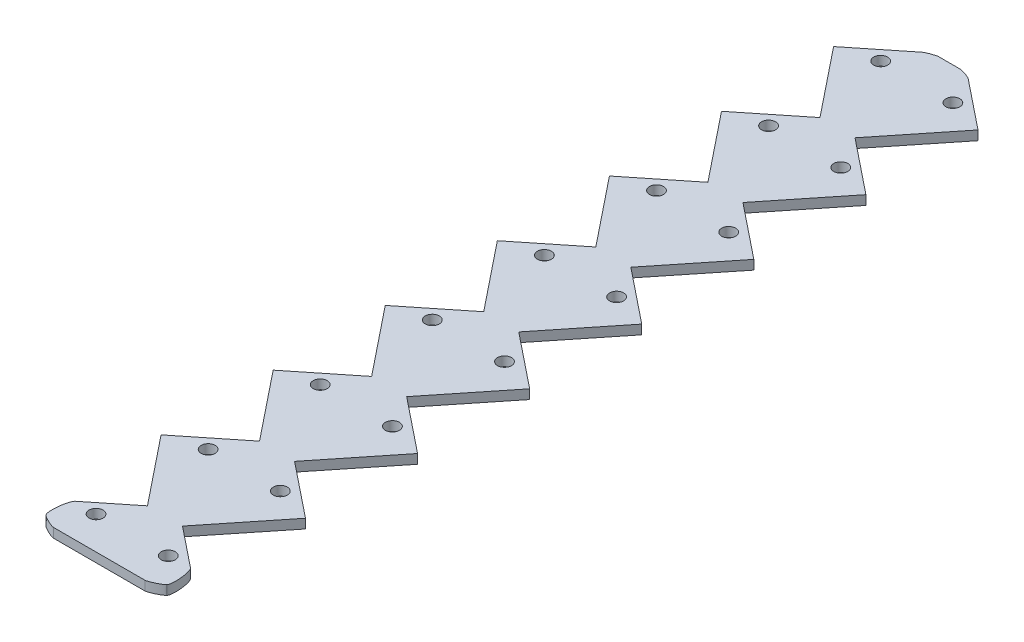
SolidWorks part; units mm, degrees
ref_plane "Front Plane" through (0, 0, 0) normal (0, 0, 1) x (1, 0, 0)
ref_plane "Top Plane" through (0, 0, 0) normal (0, 1, 0) x (1, 0, 0)
ref_plane "Right Plane" through (0, 0, 0) normal (1, 0, 0) x (0, 0, -1)
sketch "Sketch1" plane through (0, 0, 0) normal (0, 1, 0) x (1, 0, 0)
  line L0 (-13.635, -43.1454) -> (0.2556, -60.4948) construction
  line L5 (-13.635, -43.1454) -> (-22.9293, -50.5868) construction
  line L6 (-22.9293, -50.5868) -> (-9.0387, -67.9362) construction
  line L7 (-22.1678, 36.7724) -> (28.6322, 36.7724) construction
  line L8 (-22.1678, 36.7724) -> (-22.1678, -191.8276) construction
  line L9 (-22.1678, -191.8276) -> (28.6322, -191.8276) construction
  line L10 (28.6322, 36.7724) -> (28.6322, -191.8276) construction
  line L11 (0.2556, -60.4948) -> (-9.0387, -67.9362) construction
  line L12 (-13.635, -24.0954) -> (0.2556, -41.4448) construction
  line L13 (-13.635, -24.0954) -> (-22.9293, -31.5368) construction
  line L14 (-22.9293, -31.5368) -> (-9.0387, -48.8862) construction
  line L15 (-8.1122, -59.5683) -> (-27.1622, -59.5683) construction
  line L16 (-8.1122, -59.5683) -> (-8.1122, -40.5183) construction
  line L17 (0.2556, -41.4448) -> (-9.0387, -48.8862) construction
  line L18 (-8.1122, -40.5183) -> (-27.1622, -40.5183) construction
  line L19 (-8.1122, -40.5183) -> (-8.1122, -21.4683) construction
  line L20 (-13.635, -100.2954) -> (0.2556, -117.6448) construction
  line L21 (-13.635, -100.2954) -> (-22.9293, -107.7368) construction
  line L22 (-22.9293, -107.7368) -> (-9.0387, -125.0862) construction
  line L23 (0.2556, -117.6448) -> (-9.0387, -125.0862) construction
  line L24 (-13.635, -81.2454) -> (0.2556, -98.5948) construction
  line L25 (-13.635, -81.2454) -> (-22.9293, -88.6868) construction
  line L26 (-22.9293, -88.6868) -> (-9.0387, -106.0362) construction
  line L27 (-8.1122, -116.7183) -> (-27.1622, -116.7183) construction
  line L28 (-8.1122, -116.7183) -> (-8.1122, -97.6683) construction
  line L29 (0.2556, -98.5948) -> (-9.0387, -106.0362) construction
  line L30 (-8.1122, -97.6683) -> (-27.1622, -97.6683) construction
  line L31 (-8.1122, -97.6683) -> (-8.1122, -78.6183) construction
  line L32 (-13.635, -5.0454) -> (0.2556, -22.3948) construction
  line L33 (-13.635, -5.0454) -> (-22.9293, -12.4868) construction
  line L34 (-13.635, 14.0046) -> (0.2556, -3.3448) construction
  line L35 (-13.635, 14.0046) -> (-22.9293, 6.5632) construction
  line L36 (-22.9293, 6.5632) -> (-9.0387, -10.7862) construction
  line L37 (0.2556, -3.3448) -> (-9.0387, -10.7862) construction
  line L38 (-22.9293, -12.4868) -> (-9.0387, -29.8362) construction
  line L39 (0.2556, -22.3948) -> (-9.0387, -29.8362) construction
  line L40 (-13.635, 33.0546) -> (0.2556, 15.7052) construction
  line L41 (-13.635, 33.0546) -> (-22.9293, 25.6132) construction
  line L42 (-22.9293, 25.6132) -> (-9.0387, 8.2638) construction
  line L43 (0.2556, 15.7052) -> (-9.0387, 8.2638) construction
  line L44 (-8.1122, -21.4683) -> (-27.1622, -21.4683) construction
  line L45 (-8.1122, -21.4683) -> (-8.1122, -2.4183) construction
  line L46 (-13.635, -62.1954) -> (0.2556, -79.5448) construction
  line L47 (-13.635, -62.1954) -> (-22.9293, -69.6368) construction
  line L48 (-22.9293, -69.6368) -> (-9.0387, -86.9862) construction
  line L49 (0.2556, -79.5448) -> (-9.0387, -86.9862) construction
  line L50 (-8.1122, -78.6183) -> (-27.1622, -78.6183) construction
  line L51 (-8.1122, -78.6183) -> (-8.1122, -59.5683) construction
  line L52 (-8.1122, -2.4183) -> (-27.1622, -2.4183) construction
  line L53 (-8.1122, -2.4183) -> (-8.1122, 16.6317) construction
  line L54 (-8.1122, 16.6317) -> (-27.1622, 16.6317) construction
  line L55 (-8.1122, 16.6317) -> (-8.1122, 35.6817) construction
  line L56 (-22.9293, 25.6132) -> (-25.9059, 29.3309) construction
  line L57 (-25.9059, 29.3309) -> (-16.6116, 36.7724) construction
  line L58 (-16.6116, 36.7724) -> (-13.635, 33.0546) construction
  line L59 (-24.4176, 27.4721) -> (-15.1233, 34.9135) construction
  line L60 (-25.9059, 28.8165) -> (-25.9059, 40.1202) construction
  line L61 (-9.0387, 8.2638) -> (-6.0621, 4.5461) construction
  line L62 (-8.1122, 36.5878) -> (-8.1122, -24.5097) construction
  line L63 (-6.0621, 4.5461) -> (3.2322, 11.9875) construction
  line L64 (0.2556, 15.7052) -> (3.2322, 11.9875) construction
  line L65 (1.7439, 13.8464) -> (-7.5504, 6.405) construction
  line L66 (-19.7704, 30.6783) -> (-19.7704, 38.979) construction
  line L67 (-2.9032, 9.6112) -> (-2.9032, 17.9119) construction
  line L68 (3.2322, 11.4731) -> (3.2322, 48.1829) construction
  line L69 (4.7205, 13.8464) -> (14.0148, 6.405) construction
  line L70 (6.2088, 15.7052) -> (3.2322, 11.9875) construction
  line L71 (12.5265, 4.5461) -> (3.2322, 11.9875) construction
  line L72 (15.5031, 8.2638) -> (12.5265, 4.5461) construction
  line L73 (30.882, 27.4721) -> (21.5877, 34.9135) construction
  line L74 (23.0759, 36.7724) -> (20.0994, 33.0546) construction
  line L75 (32.3703, 29.3309) -> (23.0759, 36.7724) construction
  line L76 (29.3937, 25.6132) -> (32.3703, 29.3309) construction
  line L77 (14.5766, 16.6317) -> (14.5766, 35.6817) construction
  line L78 (14.5766, 16.6317) -> (33.6266, 16.6317) construction
  line L79 (14.5766, -2.4183) -> (14.5766, 16.6317) construction
  line L80 (14.5766, -2.4183) -> (33.6266, -2.4183) construction
  line L81 (14.5766, -78.6183) -> (14.5766, -59.5683) construction
  line L82 (14.5766, -78.6183) -> (33.6266, -78.6183) construction
  line L83 (6.2088, -79.5448) -> (15.5031, -86.9862) construction
  line L84 (29.3937, -69.6368) -> (15.5031, -86.9862) construction
  line L85 (20.0994, -62.1954) -> (29.3937, -69.6368) construction
  line L86 (20.0994, -62.1954) -> (6.2088, -79.5448) construction
  line L87 (14.5766, -21.4683) -> (14.5766, -2.4183) construction
  line L88 (14.5766, -21.4683) -> (33.6266, -21.4683) construction
  line L89 (6.2088, 15.7052) -> (15.5031, 8.2638) construction
  line L90 (29.3937, 25.6132) -> (15.5031, 8.2638) construction
  line L91 (20.0994, 33.0546) -> (29.3937, 25.6132) construction
  line L92 (20.0994, 33.0546) -> (6.2088, 15.7052) construction
  line L93 (6.2088, -22.3948) -> (15.5031, -29.8362) construction
  line L94 (29.3937, -12.4868) -> (15.5031, -29.8362) construction
  line L95 (6.2088, -3.3448) -> (15.5031, -10.7862) construction
  line L96 (29.3937, 6.5632) -> (15.5031, -10.7862) construction
  line L97 (20.0994, 14.0046) -> (29.3937, 6.5632) construction
  line L98 (20.0994, 14.0046) -> (6.2088, -3.3448) construction
  line L99 (20.0994, -5.0454) -> (29.3937, -12.4868) construction
  line L100 (20.0994, -5.0454) -> (6.2088, -22.3948) construction
  line L101 (14.5766, -97.6683) -> (14.5766, -78.6183) construction
  line L102 (14.5766, -97.6683) -> (33.6266, -97.6683) construction
  line L103 (6.2088, -98.5948) -> (15.5031, -106.0362) construction
  line L104 (14.5766, -116.7183) -> (14.5766, -97.6683) construction
  line L105 (14.5766, -116.7183) -> (33.6266, -116.7183) construction
  line L106 (29.3937, -88.6868) -> (15.5031, -106.0362) construction
  line L107 (20.0994, -81.2454) -> (29.3937, -88.6868) construction
  line L108 (20.0994, -81.2454) -> (6.2088, -98.5948) construction
  line L109 (6.2088, -117.6448) -> (15.5031, -125.0862) construction
  line L110 (29.3937, -107.7368) -> (15.5031, -125.0862) construction
  line L111 (20.0994, -100.2954) -> (29.3937, -107.7368) construction
  line L112 (20.0994, -100.2954) -> (6.2088, -117.6448) construction
  line L113 (14.5766, -40.5183) -> (14.5766, -21.4683) construction
  line L114 (14.5766, -40.5183) -> (33.6266, -40.5183) construction
  line L115 (6.2088, -41.4448) -> (15.5031, -48.8862) construction
  line L116 (14.5766, -59.5683) -> (14.5766, -40.5183) construction
  line L117 (14.5766, -59.5683) -> (33.6266, -59.5683) construction
  line L118 (29.3937, -31.5368) -> (15.5031, -48.8862) construction
  line L119 (20.0994, -24.0954) -> (29.3937, -31.5368) construction
  line L120 (20.0994, -24.0954) -> (6.2088, -41.4448) construction
  line L121 (6.2088, -60.4948) -> (15.5031, -67.9362) construction
  line L122 (29.3937, -50.5868) -> (15.5031, -67.9362) construction
  line L123 (20.0994, -43.1454) -> (29.3937, -50.5868) construction
  line L124 (20.0994, -43.1454) -> (6.2088, -60.4948) construction
  line L125 (23.0759, 36.7724) -> (-16.6116, 36.7724) construction
  circle A2 centre (-8.1122, -59.5683) radius 5.9531 construction
  circle A3 centre (-8.1122, -59.5683) radius 19.05 construction
  circle A4 centre (-8.1122, -40.5183) radius 5.9531 construction
  circle A5 centre (-8.1122, -40.5183) radius 19.05 construction
  circle A6 centre (-8.1122, -116.7183) radius 5.9531 construction
  circle A7 centre (-8.1122, -116.7183) radius 19.05 construction
  circle A8 centre (-8.1122, -97.6683) radius 5.9531 construction
  circle A9 centre (-8.1122, -97.6683) radius 19.05 construction
  circle A10 centre (-8.1122, -2.4183) radius 5.9531 construction
  circle A11 centre (-8.1122, -2.4183) radius 19.05 construction
  circle A12 centre (-8.1122, 16.6317) radius 5.9531 construction
  circle A13 centre (-8.1122, 16.6317) radius 19.05 construction
  circle A14 centre (-8.1122, -21.4683) radius 5.9531 construction
  circle A15 centre (-8.1122, -21.4683) radius 19.05 construction
  circle A16 centre (-8.1122, -78.6183) radius 5.9531 construction
  circle A17 centre (-8.1122, -78.6183) radius 19.05 construction
  circle A18 centre (-19.7704, 31.1928) radius 1.1906
  circle A19 centre (-2.9032, 10.1257) radius 1.1906
  circle A20 centre (14.5766, -78.6183) radius 19.05 construction
  circle A21 centre (14.5766, -78.6183) radius 5.9531 construction
  circle A22 centre (14.5766, -21.4683) radius 19.05 construction
  circle A23 centre (14.5766, -21.4683) radius 5.9531 construction
  circle A24 centre (14.5766, 16.6317) radius 19.05 construction
  circle A25 centre (14.5766, 16.6317) radius 5.9531 construction
  circle A26 centre (14.5766, -2.4183) radius 19.05 construction
  circle A27 centre (14.5766, -2.4183) radius 5.9531 construction
  circle A28 centre (14.5766, -97.6683) radius 19.05 construction
  circle A29 centre (14.5766, -97.6683) radius 5.9531 construction
  circle A30 centre (14.5766, -116.7183) radius 19.05 construction
  circle A31 centre (14.5766, -116.7183) radius 5.9531 construction
  circle A32 centre (14.5766, -40.5183) radius 19.05 construction
  circle A33 centre (14.5766, -40.5183) radius 5.9531 construction
  circle A34 centre (14.5766, -59.5683) radius 19.05 construction
  circle A35 centre (14.5766, -59.5683) radius 5.9531 construction
  circle A36 centre (9.3676, 10.1257) radius 1.1906
  circle A37 centre (26.2348, 31.1928) radius 1.1906
  point P81 (-15.1233, 34.9135)
  point P97 (3.2322, 36.7724)
  dimension "D3" = 2.3813
  dimension "D23" = 38.1
  dimension "D1" = 4.7625
  dimension "D4" = 50.8
  dimension "D5" = 228.6
  dimension "D21" = 22.225
  dimension "D22" = 11.9062
sketch "Sketch2" plane through (0, 0, 0) normal (0, 1, 0) x (1, 0, 0)
  line L0 (-16.6116, 36.7724) -> (-13.635, 33.0546)
  line L1 (-13.635, 33.0546) -> (-22.9293, 25.6132)
  line L2 (-22.9293, 25.6132) -> (-13.635, 14.0046)
  line L3 (-18.2822, 10.2839) -> (-19.7704, 12.1428)
  line L4 (-13.635, 14.0046) -> (-22.9293, 6.5632) construction
  line L5 (-19.7704, -199969.3217) -> (-19.7704, 200038.979) construction
  line L6 (3.2322, 37.6418) -> (3.2322, 34.7632) construction
  line L7 (-9.0387, -10.7862) -> (0.2556, -22.3948)
  line L8 (3.2322, -199988.5269) -> (3.2322, 200048.1829) construction
  line L9 (-13.635, 14.0046) -> (-22.9293, 6.5632)
  line L10 (-22.9293, 6.5632) -> (-13.635, -5.0454)
  line L11 (-13.635, -5.0454) -> (-22.9293, -12.4868)
  line L12 (-22.9293, -12.4868) -> (-13.635, -24.0954)
  line L13 (-13.635, -24.0954) -> (-22.9293, -31.5368)
  line L14 (-22.9293, -31.5368) -> (-13.635, -43.1454)
  line L15 (-13.635, -43.1454) -> (-22.9293, -50.5868)
  line L16 (-22.9293, -50.5868) -> (-13.635, -62.1954)
  line L17 (-13.635, -62.1954) -> (-22.9293, -69.6368)
  line L18 (-22.9293, -69.6368) -> (-13.635, -81.2454)
  line L19 (-13.635, -81.2454) -> (-22.9293, -88.6868)
  line L20 (-22.9293, -88.6868) -> (-13.635, -100.2954)
  line L21 (-13.635, -100.2954) -> (-22.9293, -107.7368)
  line L22 (-22.9293, -107.7368) -> (-13.635, -119.3454)
  line L23 (0.2556, 15.7052) -> (-9.0387, 8.2638)
  line L24 (-9.0387, 8.2638) -> (0.2556, -3.3448)
  line L25 (0.2556, -3.3448) -> (-9.0387, -10.7862)
  line L26 (-9.0387, -29.8362) -> (0.2556, -41.4448)
  line L27 (0.2556, -22.3948) -> (-9.0387, -29.8362)
  line L28 (-9.0387, -48.8862) -> (0.2556, -60.4948)
  line L29 (0.2556, -41.4448) -> (-9.0387, -48.8862)
  line L30 (-9.0387, -67.9362) -> (0.2556, -79.5448)
  line L31 (0.2556, -60.4948) -> (-9.0387, -67.9362)
  line L32 (-9.0387, -86.9862) -> (0.2556, -98.5948)
  line L33 (0.2556, -79.5448) -> (-9.0387, -86.9862)
  line L34 (-9.0387, -106.0362) -> (0.2556, -117.6448)
  line L35 (0.2556, -98.5948) -> (-9.0387, -106.0362)
  line L37 (0.2556, -117.6448) -> (-9.0387, -125.0862)
  line L38 (6.2088, -117.6448) -> (15.5031, -125.0862)
  line L39 (-9.0387, -125.0862) -> (0.2556, -136.6948) [skipped]
  line L41 (-22.9293, 25.6132) -> (-27.6918, 25.6132) construction
  line L42 (-16.6116, 36.7724) -> (-27.6918, 36.7724)
  line L43 (-27.6918, 36.7724) -> (-27.6918, -124.1079)
  line L44 (-13.635, -119.3454) -> (-13.635, -124.1079)
  line L45 (-13.635, -124.1079) -> (-27.6918, -124.1079)
  line L47 (6.2088, -98.5948) -> (15.5031, -106.0362)
  line L48 (15.5031, -106.0362) -> (6.2088, -117.6448)
  line L49 (6.2088, -79.5448) -> (15.5031, -86.9862)
  line L50 (15.5031, -86.9862) -> (6.2088, -98.5948)
  line L51 (6.2088, -60.4948) -> (15.5031, -67.9362)
  line L52 (15.5031, -67.9362) -> (6.2088, -79.5448)
  line L53 (6.2088, -41.4448) -> (15.5031, -48.8862)
  line L54 (15.5031, -48.8862) -> (6.2088, -60.4948)
  line L55 (6.2088, -22.3948) -> (15.5031, -29.8362)
  line L56 (15.5031, -29.8362) -> (6.2088, -41.4448)
  line L57 (6.2088, -3.3448) -> (15.5031, -10.7862)
  line L58 (15.5031, 8.2638) -> (6.2088, -3.3448)
  line L59 (6.2088, 15.7052) -> (15.5031, 8.2638)
  line L60 (15.5031, -10.7862) -> (6.2088, -22.3948)
  line L61 (0.2556, 15.7052) -> (6.2088, 15.7052)
  line L62 (29.3937, 25.6132) -> (34.1562, 25.6132) construction
  line L63 (20.0994, -124.1079) -> (34.1562, -124.1079)
  line L64 (20.0994, -119.3454) -> (20.0994, -124.1079)
  line L65 (34.1562, 36.7724) -> (34.1562, -124.1079)
  line L66 (23.0759, 36.7724) -> (34.1562, 36.7724)
  line L67 (29.3937, -107.7368) -> (20.0994, -119.3454)
  line L68 (20.0994, -100.2954) -> (29.3937, -107.7368)
  line L69 (29.3937, -88.6868) -> (20.0994, -100.2954)
  line L70 (20.0994, -81.2454) -> (29.3937, -88.6868)
  line L71 (29.3937, -69.6368) -> (20.0994, -81.2454)
  line L72 (20.0994, -62.1954) -> (29.3937, -69.6368)
  line L73 (29.3937, -50.5868) -> (20.0994, -62.1954)
  line L74 (20.0994, -43.1454) -> (29.3937, -50.5868)
  line L75 (29.3937, -31.5368) -> (20.0994, -43.1454)
  line L76 (20.0994, -24.0954) -> (29.3937, -31.5368)
  line L77 (29.3937, -12.4868) -> (20.0994, -24.0954)
  line L78 (20.0994, -5.0454) -> (29.3937, -12.4868)
  line L79 (29.3937, 6.5632) -> (20.0994, -5.0454)
  line L80 (20.0994, 14.0046) -> (29.3937, 6.5632)
  line L81 (24.7465, 10.2839) -> (26.2348, 12.1428)
  line L82 (29.3937, 25.6132) -> (20.0994, 14.0046)
  line L83 (20.0994, 33.0546) -> (29.3937, 25.6132)
  line L84 (23.0759, 36.7724) -> (20.0994, 33.0546)
  line L85 (-27.6918, 31.9683) -> (-21.6916, 36.7724)
  line L86 (28.1559, 36.7724) -> (34.1562, 31.9683)
  line L87 (-22.9293, -107.7368) -> (-27.6918, -101.7884)
  line L88 (29.3937, -107.7368) -> (34.1562, -101.7884)
  line L89 (-9.0387, -125.0862) -> (-6.0621, -128.8039)
  line L90 (15.5031, -125.0862) -> (12.5265, -128.8039)
  line L91 (-6.0621, -128.8039) -> (12.5265, -128.8039)
  line L92 (-25.9059, 29.3309) -> (-16.6116, 36.7724) construction
  line L93 (32.3703, 29.3309) -> (23.0759, 36.7724) construction
  circle A0 centre (-19.7704, 31.1928) radius 1.1906
  circle A1 centre (-19.7704, 31.1928) radius 1.1906 construction
  circle A2 centre (-19.7704, 12.1428) radius 1.1906
  circle A3 centre (-19.7704, -6.9072) radius 1.1906
  circle A4 centre (-19.7704, -25.9572) radius 1.1906
  circle A5 centre (-19.7704, -45.0072) radius 1.1906
  circle A6 centre (-19.7704, -64.0572) radius 1.1906
  circle A7 centre (-19.7704, -83.1072) radius 1.1906
  circle A8 centre (-19.7704, -102.1572) radius 1.1906
  circle A9 centre (-2.9032, 10.1257) radius 1.1906
  circle A10 centre (-2.9032, 10.1257) radius 1.1906 construction
  circle A11 centre (-2.9032, -8.9243) radius 1.1906
  circle A12 centre (-2.9032, -27.9743) radius 1.1906
  circle A13 centre (-2.9032, -47.0243) radius 1.1906
  circle A14 centre (-2.9032, -66.0743) radius 1.1906
  circle A15 centre (-2.9032, -85.1243) radius 1.1906
  circle A16 centre (-2.9032, -104.1743) radius 1.1906
  circle A17 centre (-2.9032, -123.2243) radius 1.1906
  circle A18 centre (9.3676, -123.2243) radius 1.1906
  circle A19 centre (9.3676, -104.1743) radius 1.1906
  circle A20 centre (9.3676, -85.1243) radius 1.1906
  circle A21 centre (9.3676, -66.0743) radius 1.1906
  circle A22 centre (9.3676, -47.0243) radius 1.1906
  circle A23 centre (9.3676, -27.9743) radius 1.1906
  circle A24 centre (9.3676, -8.9243) radius 1.1906
  circle A25 centre (9.3676, 10.1257) radius 1.1906
  circle A26 centre (26.2348, -102.1572) radius 1.1906
  circle A27 centre (26.2348, -83.1072) radius 1.1906
  circle A28 centre (26.2348, -64.0572) radius 1.1906
  circle A29 centre (26.2348, -45.0072) radius 1.1906
  circle A30 centre (26.2348, -25.9572) radius 1.1906
  circle A31 centre (26.2348, -6.9072) radius 1.1906
  circle A32 centre (26.2348, 12.1428) radius 1.1906
  circle A33 centre (26.2348, 31.1928) radius 1.1906
  dimension "D1" = 19.05
  dimension "D3" = 8
  dimension "D2" = 8
  dimension "D4" = 3.175
  dimension "D5" = 3.175
extrude "Boss-Extrude1" add sketch "Sketch2" along normal blind 1.5875 contours L89 L91 L90 L38 L48 L47 L50 L49 L52 L51 L54 L53 L56 L55 L60 L57 L58 L59 L61 L23 L24 L25 L7 L27 L26 L29 L28 L31 L30 L33 L32 L35 L34 L37 A24 A22 A20 A18 A17 A16 A15 A14 region at (3.2322, 0, 56.9536)
fillet "Fillet1" radius 3.175 6 edges at (6.2088, 0.7937, -15.7052) (0.2556, 0.7937, -15.7052) (-9.0387, 0.7937, 125.0862) (15.5031, 0.7937, 125.0862) (12.5265, 0.7937, 128.8039) (-6.0621, 0.7937, 128.8039) conic radius 10
